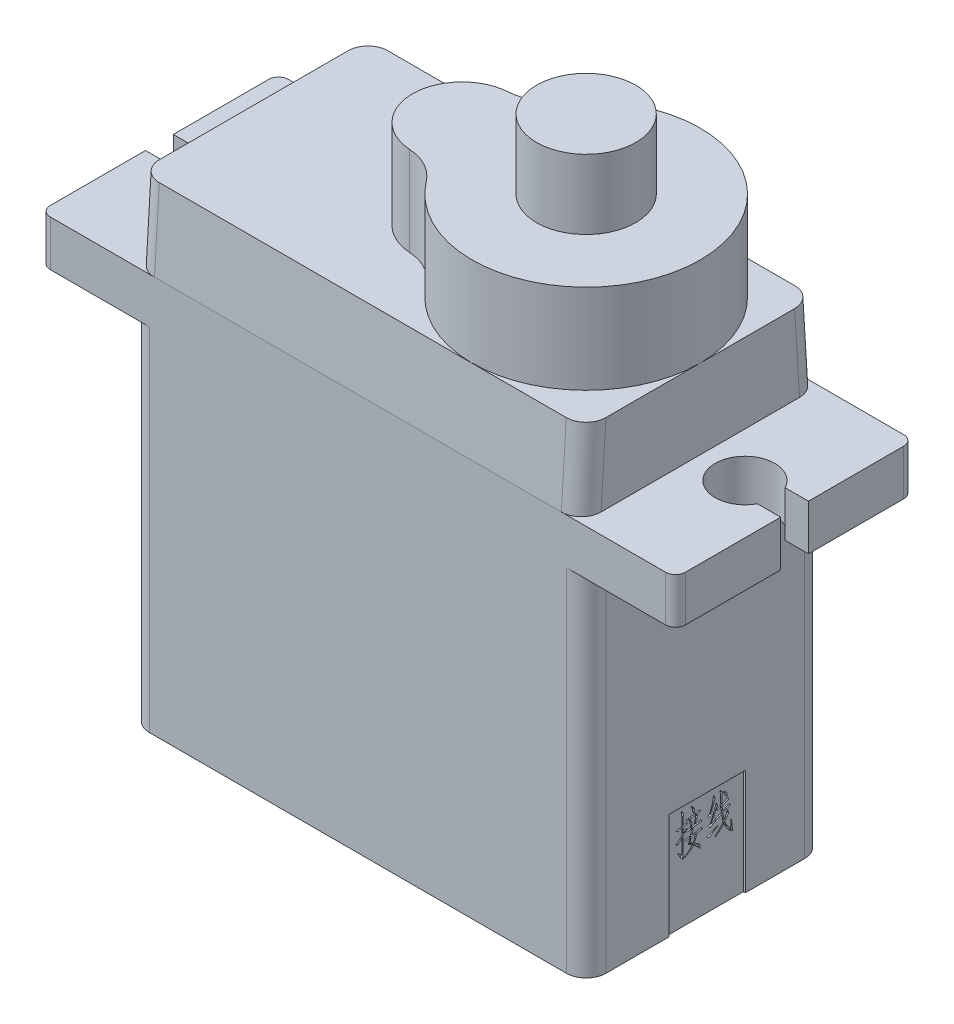
SolidWorks part; units mm, degrees
ref_plane "前视基准面" through (0, 0, 0) normal (0, 0, 1) x (1, 0, 0)
ref_plane "上视基准面" through (0, 0, 0) normal (0, 1, 0) x (1, 0, 0)
ref_plane "右视基准面" through (0, 0, 0) normal (1, 0, 0) x (0, 0, -1)
other "Configuration Table"
sketch "草图1" plane through (0, 0, 0) normal (0, 1, 0) x (1, 0, 0)
  line L1 (-11.5, 6) -> (11.5, 6)
  line L2 (-11.5, 6) -> (-11.5, -6)
  line L3 (-11.5, -6) -> (11.5, -6)
  line L4 (11.5, 6) -> (11.5, -6)
  line L5 (-11.5, 6) -> (11.5, -6) construction
  line L6 (-11.5, -6) -> (11.5, 6) construction
  point P0 (0, 0)
  dimension "D1" = 12
  dimension "D2" = 23
extrude "凸台-拉伸1" add sketch "草图1" along normal blind 20
sketch "草图2" plane through (0, 20, 0) normal (0, 1, 0) x (1, 0, 0)
  line L0 (-16, 0) -> (16, 0) construction
  line L1 (-16, 6) -> (16, 6)
  line L2 (-16, 6) -> (-16, -6)
  line L3 (-16, -6) -> (16, -6)
  line L4 (16, 6) -> (16, -6)
  line L5 (-16, 6) -> (16, -6) construction
  line L6 (-16, -6) -> (16, 6) construction
  line L8 (-17.9894, 0.7) -> (-14.0106, 0.7)
  line L9 (-17.9894, 0.7) -> (-17.9894, -0.7)
  line L10 (-17.9894, -0.7) -> (-14.0106, -0.7)
  line L11 (-14.0106, 0.7) -> (-14.0106, -0.7)
  line L12 (-17.9894, 0.7) -> (-14.0106, -0.7) construction
  line L13 (-17.9894, -0.7) -> (-14.0106, 0.7) construction
  line L14 (17.9338, 0.7) -> (14.0662, 0.7)
  line L15 (17.9338, 0.7) -> (17.9338, -0.7)
  line L16 (17.9338, -0.7) -> (14.0662, -0.7)
  line L17 (14.0662, 0.7) -> (14.0662, -0.7)
  line L18 (17.9338, 0.7) -> (14.0662, -0.7) construction
  line L19 (17.9338, -0.7) -> (14.0662, 0.7) construction
  circle A0 centre (-13.5, 0) radius 1.5
  circle A1 centre (13.5, 0) radius 1.5
  point P0 (0, 0)
  line M5 (11.5, -6) -> (11.5, 6)
  line M7 (-11.5, 6) -> (-11.5, -6)
  dimension "D2" = 3
  dimension "D3" = 3
  dimension "D4" = 13.5
  dimension "D5" = 27
  dimension "D1" = 32
  dimension "D6" = 1.4
  dimension "D7" = 1.4
extrude "凸台-拉伸2" add sketch "草图2" against normal blind 2.3 contours A0 L10 L2 L3 L1 L8 M7 | A1 L14 L4 L1 L3 L16 M5 region at (-13.75, 20, -5.8718) region at (13.75, 20, -5.8718)
sketch "草图5" plane through (0, 20, 0) normal (0, 1, 0) x (1, 0, 0)
  line L1 (-11.25, 5.75) -> (11.25, 5.75)
  line L2 (-11.25, 5.75) -> (-11.25, -5.75)
  line L3 (-11.25, -5.75) -> (11.25, -5.75)
  line L4 (11.25, 5.75) -> (11.25, -5.75)
  line L5 (-11.25, 5.75) -> (11.25, -5.75) construction
  line L6 (-11.25, -5.75) -> (11.25, 5.75) construction
  point P0 (0, 0)
  dimension "D1" = 22.5
  dimension "D2" = 11.5
extrude "凸台-拉伸4" add sketch "草图5" along normal blind 4
chamfer "倒角1" distance 0.25 angle 86.5 1 edges at (0, 20, 5.75) first distance on face at (0, 20, 0)
chamfer "倒角2" distance 0.25 angle 86.5 1 edges at (0, 20, -5.75) first distance on face at (0, 20, 0.0312)
sketch "草图6" plane through (0, 24, 0) normal (0, 1, 0) x (1, 0, 0)
  line L0 (-11.25, 0) -> (11.25, 0) construction
  line L1 (-11.25, 6) -> (-11.25, -6) construction
  line L2 (11.25, -5.7553) -> (11.25, 5.7553) construction
  line L3 (-11.25, 5.7553) -> (-11.25, -5.7553) construction
  line L4 (-11.25, 5.75) -> (11.25, 5.75) construction
  line L5 (-11.25, 5.75) -> (-11.25, -5.75) construction
  line L6 (-11.25, -5.75) -> (11.25, -5.75) construction
  line L7 (11.25, 5.75) -> (11.25, -5.75) construction
  line L8 (11.25, -6) -> (11.25, 6) construction
  circle A0 centre (5.5, 0) radius 5.75
  circle A1 centre (-0.75, 0) radius 2.5
  arc A2 (-0.91, 2.4949) -> (0.9209, 3.4777) centre (-1.07, 4.9897) ccw
  arc A3 (0.9209, -3.4777) -> (-0.91, -2.4949) centre (-1.07, -4.9897) ccw
  dimension "D3" = 5
  dimension "D4" = 12
  dimension "D5" = 5
  dimension "D6" = 5
  dimension "D1" = 11.5
  dimension "D2" = 5.75
extrude "凸台-拉伸5" add sketch "草图6" along normal blind 4.5 contours A1 A0 | A0 A1 | A0 A1 | A3 A0 A1 | A2 A1 A0 region at (5.824, 24, 0) region at (0.1225, 24, -2.6532) region at (0.1225, 24, 2.6532) region at (0.6709, 24, 0) region at (-1.4581, 24, 0)
sketch "草图7" plane through (0, 28.5, 0) normal (0, 1, 0) x (1, 0, 0)
  circle A0 centre (5.5, 0) radius 2.5
  dimension "D1" = 5
extrude "切除-拉伸1" cut sketch "草图7" against normal blind 5
fillet "圆角1" radius 0.5 4 edges at (-16, 18.85, -6) (-16, 18.85, 6) (16, 18.85, 6) (16, 18.85, -6)
fillet "圆角2" radius 1 8 edges at (-11.25, 22, 5.8777) (-11.5, 8.85, 6) (11.25, 22, 5.8777) (11.5, 8.85, 6) (11.5, 8.85, -6) (11.25, 22, -5.8777) (-11.5, 8.85, -6) (-11.25, 22, -5.8777)
sketch "草图8" plane through (11.5, 0, 0) normal (1, 0, 0) x (0, 0, -1)
  line L0 (-5, 0) -> (5, 0) construction
  line L1 (-1.8169, 5.3459) -> (2.0231, 5.3459)
  line L2 (-1.8169, 5.3459) -> (-1.8169, 0)
  line L3 (-1.8169, 0) -> (2.0231, 0)
  line L4 (2.0231, 5.3459) -> (2.0231, 0)
extrude "切除-拉伸2" cut sketch "草图8" against normal blind 0.1
sketch "草图9" plane through (11.4, 0, 0) normal (1, 0, 0) x (0, 0, -1)
  text T0 "接线" font "汉仪长仿宋体" height 1.5
extrude "切除-拉伸3" cut sketch "草图9" against normal blind 0.1
sketch "草图10" plane through (0, 23.5, 0) normal (0, 1, 0) x (1, 0, 0)
  circle A0 centre (5.5, 0) radius 2.5
extrude "凸台-拉伸6" add sketch "草图10" along normal blind 8.5
